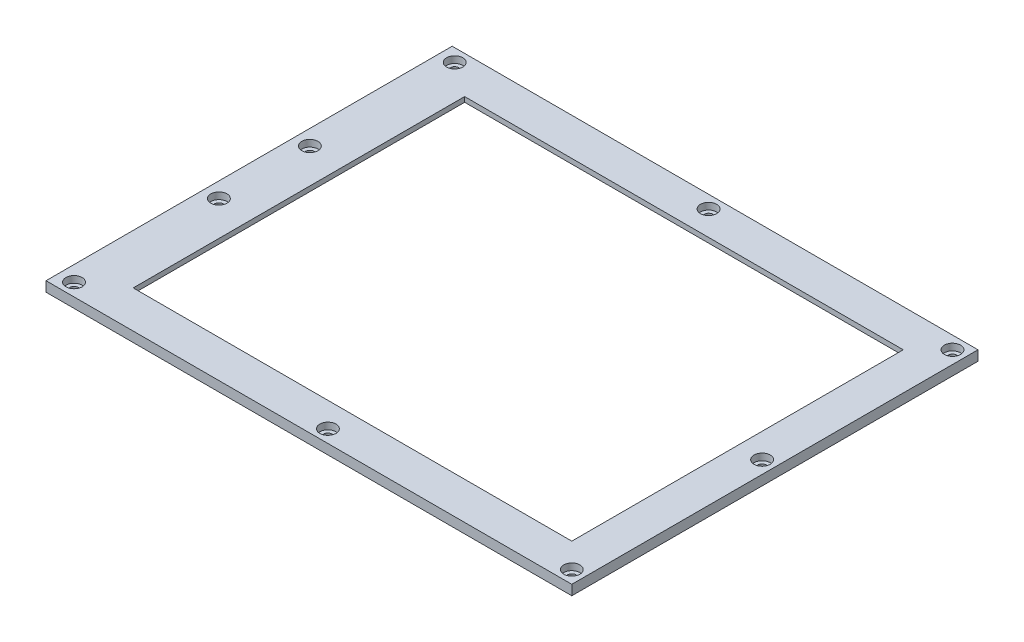
SolidWorks part; units mm, degrees
ref_plane "Front Plane" through (0, 0, 0) normal (0, 0, 1) x (1, 0, 0)
ref_plane "Top Plane" through (0, 0, 0) normal (0, 1, 0) x (1, 0, 0)
ref_plane "Right Plane" through (0, 0, 0) normal (1, 0, 0) x (0, 0, -1)
sketch "Sketch1" plane through (0, 0, 0) normal (0, 1, 0) x (1, 0, 0)
  line L1 (-88, -66.5) -> (88, -66.5)
  line L2 (-88, -66.5) -> (-88, 66.5)
  line L3 (-88, 66.5) -> (88, 66.5)
  line L4 (88, -66.5) -> (88, 66.5)
  line L5 (-88, -66.5) -> (88, 66.5) construction
  line L6 (-88, 66.5) -> (88, -66.5) construction
  line L7 (-108, -81.5) -> (103, -81.5)
  line L8 (-108, -81.5) -> (-108, 81.5)
  line L9 (-108, 81.5) -> (103, 81.5)
  line L10 (103, -81.5) -> (103, 81.5)
  point P0 (0, 0)
  point P6 (0, 0)
  dimension "D1" = 133
  dimension "D2" = 176
  dimension "D3" = 15
  dimension "D4" = 20
  dimension "D5" = 15
  dimension "D6" = 15
extrude "Boss-Extrude1" add sketch "Sketch1" along normal blind 4 contours L8 L7 L10 L9 | L2 L1 L4 L3
sketch "Sketch2" plane through (0, 4, 0) normal (0, 1, 0) x (1, 0, 0)
  line L0 (-108, -81.5) -> (-108, 81.5) construction
  line L1 (-95.75, -71.25) -> (92.75, -71.25)
  line L2 (-95.75, -71.25) -> (-95.75, -10.25)
  line L3 (-95.75, 71.25) -> (92.75, 71.25)
  line L4 (92.75, -71.25) -> (92.75, 71.25)
  line L7 (-95.75, 10.25) -> (-102.25, 10.25)
  line L9 (-95.75, -10.25) -> (-102.25, -10.25)
  line L10 (-102.25, 10.25) -> (-102.25, 6.75)
  line L11 (-102.25, 6.75) -> (-108, 6.75)
  line L13 (-102.25, -6.75) -> (-108, -6.75)
  line L14 (-108, 6.75) -> (-108, -6.75)
  line L15 (-102.25, -6.75) -> (-102.25, -10.25)
  line L16 (-95.75, 10.25) -> (-95.75, 71.25)
  line L17 (-102.25, 10.25) -> (-102.25, -10.25) construction
  line L23 (88, -66.5) -> (88, 66.5) construction
  line L24 (-88, -66.5) -> (88, -66.5) construction
  point P0 (0, 0)
  point P10 (-108, 0)
  point P17 (-102.25, 0)
  point P18 (92.75, 0)
  dimension "D1" = 188.5
  dimension "D2" = 142.5
  dimension "D3" = 20.5
  dimension "D4" = 6.5
  dimension "D5" = 13.5
  dimension "D6" = 4.75
  dimension "D7" = 4.75
extrude "Cut-Extrude1" cut sketch "Sketch2" along normal blind 2 from surface starting at face at (0, 0, 0)
hole_wizard "CBORE for M3 SHCS1" positions "Sketch5" profile "Sketch6" counterbore size "M3" standard "ANSI Metric" end condition up to next
sketch "Sketch5" plane through (0, 4, 0) normal (0, 1, 0) x (1, 0, 0)
  line L0 (-108, -81.5) -> (103, -81.5) construction
  line L1 (-95.75, -71.25) -> (92.75, -71.25) construction
  line L2 (0, -81.5) -> (0, -71.25) construction
  line L4 (0, 81.5) -> (0, 71.25) construction
  line L5 (-108, 81.5) -> (103, 81.5) construction
  line L6 (92.75, 71.25) -> (-95.75, 71.25) construction
  line L8 (-95.75, -71.25) -> (-95.75, -81.5) construction
  line L10 (-95.75, -71.25) -> (-108, -71.25) construction
  line L11 (-108, -81.5) -> (-108, -6.75) construction
  line L13 (92.75, -71.25) -> (92.75, -81.5) construction
  line L15 (92.75, -71.25) -> (103, -71.25) construction
  line L16 (103, -81.5) -> (103, 81.5) construction
  line L18 (-102.25, -10.25) -> (-95.75, -10.25) construction
  line L19 (-95.75, 10.25) -> (-102.25, 10.25) construction
  point P0 (-101.875, 76.375)
  point P2 (0, 76.375)
  point P4 (97.875, 76.375)
  point P6 (97.875, -76.375)
  point P8 (97.875, 0)
  point P10 (0, -76.375)
  point P12 (-101.875, -76.375)
  point P14 (-101.875, -18.25)
  point P16 (-101.875, 18.25)
  point P65 (-101.875, -71.25)
  point P79 (97.875, -71.25)
  dimension "D1" = 8
  dimension "D2" = 8
sketch "Sketch6" plane through (-101.875, 4, -76.375) normal (1, 0, 0) x (0, 0, 1)
  line L0 (0, 0) -> (0, 4)
  line L1 (0, 4) -> (1.7, 4)
  line L3 (1.7, 4) -> (1.7, 2.68)
  line L4 (1.7, 2.68) -> (3.25, 2.68)
  line L5 (3.25, 2.68) -> (3.25, 0)
  line L7 (3.25, 0) -> (0, 0)
  line L11 (0, -6.35) -> (0, 107.95) construction
  dimension "Thru Hole Dia." = 3.4
  dimension "Thru Hole Depth" = 4
  dimension "C'Bore Dia." = 6.5
  dimension "C'Bore Depth" = 2.68
